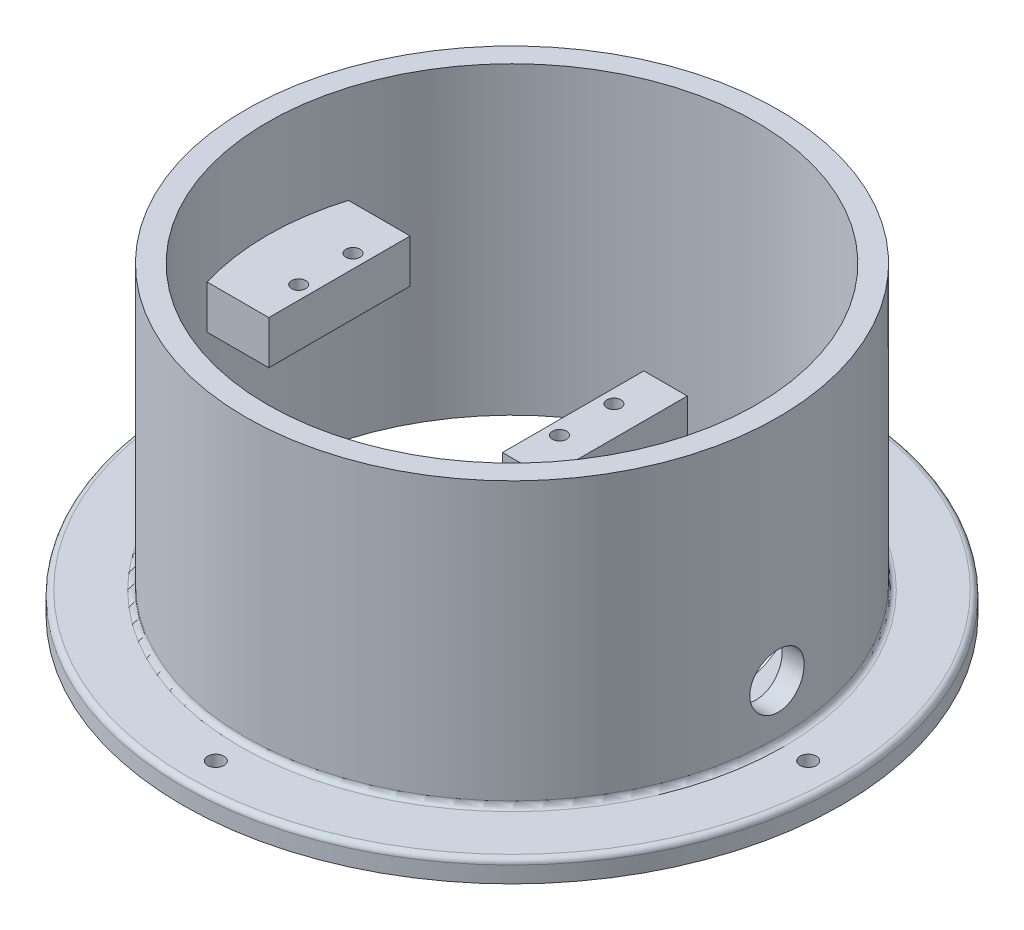
SolidWorks part; units mm, degrees
ref_plane "Front Plane" through (0, 0, 0) normal (0, 0, 1) x (1, 0, 0)
ref_plane "Top Plane" through (0, 0, 0) normal (0, 1, 0) x (1, 0, 0)
ref_plane "Right Plane" through (0, 0, 0) normal (1, 0, 0) x (0, 0, -1)
sketch "Sketch1" plane through (0, 0, 0) normal (0, 1, 0) x (1, 0, 0)
  circle A0 centre (0, 0) radius 45
  circle A1 centre (0, 0) radius 60.625
  dimension "D1" = 90
  dimension "D2" = 121.25
extrude "Boss-Extrude1" add sketch "Sketch1" along normal blind 4
sketch "Sketch2" plane through (0, 4, 0) normal (0, 1, 0) x (1, 0, 0)
  circle A1 centre (0, 0) radius 45
  circle A2 centre (0, 0) radius 49
  dimension "D1" = 90
  dimension "D2" = 98
extrude "Boss-Extrude2" add sketch "Sketch2" along normal blind 52
sketch "Sketch3" plane through (0, 0, 0) normal (0, 0, 1) x (1, 0, 0)
  line L0 (-60.625, 0) -> (60.625, 0) construction
  line L1 (11.25, 0) -> (19.25, 0)
  line L2 (11.25, 0) -> (11.25, 38)
  line L3 (11.25, 38) -> (19.25, 38)
  line L4 (19.25, 0) -> (19.25, 38)
  line L5 (45, 56) -> (-45, 56) construction
  line L6 (-46.75, 38) -> (-31.75, 38)
  line L7 (-46.75, 38) -> (-46.75, 30)
  line L8 (-46.75, 30) -> (-31.75, 30)
  line L9 (-31.75, 38) -> (-31.75, 30)
  dimension "D1" = 8
  dimension "D2" = 11.25
  dimension "D3" = 38
  dimension "D4" = 43
  dimension "D5" = 8
  dimension "D6" = 15
  dimension "D7" = 18
extrude "Boss-Extrude3" add sketch "Sketch3" along normal mid plane 26
sketch "Sketch4" plane through (11.25, 0, 0) normal (-1, 0, 0) x (0, 0, 1)
  line L0 (0, 0) -> (0, 56) construction
  line L1 (45, 56) -> (-45, 56) construction
  line L3 (-5, 29) -> (5, 29)
  line L4 (-5, 29) -> (-5, 5)
  line L5 (-5, 5) -> (5, 5)
  line L6 (5, 29) -> (5, 5)
  line L7 (-5, 29) -> (5, 5) construction
  line L8 (-5, 5) -> (5, 29) construction
  point P5 (0, 17)
  dimension "D1" = 5
  dimension "D2" = 24
  dimension "D3" = 10
extrude "Cut-Extrude1" cut sketch "Sketch4" against normal up to next (8 mm away)
sketch "Sketch5" plane through (11.25, 0, 0) normal (-1, 0, 0) x (0, 0, 1)
  line L0 (0, 0) -> (0, 56) construction
  line L1 (49, 56) -> (-49, 56) construction
  circle A0 centre (0, 14) radius 5
  dimension "D2" = 10
  dimension "D1" = 14
extrude "Cut-Extrude2" cut sketch "Sketch5" against normal through all
sketch "Sketch6" plane through (0, 38, 0) normal (0, 1, 0) x (1, 0, 0)
  line L0 (45, 0) -> (-45, 0) construction
  line L1 (-31.75, -13) -> (-31.75, 13) construction
  line L2 (-34.25, 5) -> (13.75, 5) construction
  line L3 (-34.25, 5) -> (-34.25, -5) construction
  line L4 (-34.25, -5) -> (13.75, -5) construction
  line L5 (13.75, 5) -> (13.75, -5) construction
  line L6 (11.25, -13) -> (11.25, 13) construction
  arc A1 (-43.0813, 13) -> (-43.0813, -13) centre (0, 0) ccw construction
  circle A2 centre (-34.25, 5) radius 1.3
  circle A3 centre (-34.25, -5) radius 1.3
  circle A4 centre (13.75, -5) radius 1.3
  circle A5 centre (13.75, 5) radius 1.3
  point P7 (0, 0)
  dimension "D5" = 2.6
  dimension "D1" = 5
  dimension "D2" = 5
  dimension "D3" = 2.5
  dimension "D4" = 2.5
extrude "Cut-Extrude3" cut sketch "Sketch6" against normal blind 7.2
sketch "Sketch7" plane through (0, 0, 0) normal (0, -1, 0) x (1, 0, 0)
  line L0 (11.25, 13) -> (25.2498, 37.2484)
  line L1 (19.25, 0) -> (72.1503, 0) construction
  line L2 (19.25, 13) -> (19.25, -13) construction
  line L3 (11.25, -13) -> (25.2498, -37.2484)
  line L4 (11.25, 13) -> (11.25, -13)
  line L5 (24.25, 19.5167) -> (27.3618, 24.9065)
  line L6 (24.25, -19.5167) -> (27.3618, -24.9065)
  line L8 (24.25, 19.5167) -> (24.25, -19.5167)
  line L9 (19.25, 10.8564) -> (27.3618, 24.9065) construction
  line L10 (19.25, 10.8564) -> (19.25, -10.8564) construction
  line L11 (19.25, -10.8564) -> (27.3618, -24.9065) construction
  circle A0 centre (0, 0) radius 45 construction
  arc A1 (25.2498, -37.2484) -> (25.2498, 37.2484) centre (0, 0) ccw
  arc A2 (27.3618, -24.9065) -> (27.3618, 24.9065) centre (0, 0) ccw
  dimension "D1" = 60
  dimension "D3" = 5
  dimension "D2" = 8
extrude "Boss-Extrude5" add sketch "Sketch7" against normal blind 4
sketch "Sketch8" plane through (0, 0, 0) normal (0, -1, 0) x (1, 0, 0)
  circle A0 centre (0, 0) radius 54.5 construction
  circle A1 centre (54.5, 0) radius 1.5
  circle A2 centre (0, -54.5) radius 1.5
  circle A3 centre (-54.5, 0) radius 1.5
  circle A4 centre (0, 54.5) radius 1.5
  dimension "D1" = 109
  dimension "D2" = 3
  dimension "D3" = 4
extrude "Cut-Extrude4" cut sketch "Sketch8" against normal through all
fillet "Fillet1" radius 1 2 edges at (0, 4, 60.625) (0, 4, 49)
